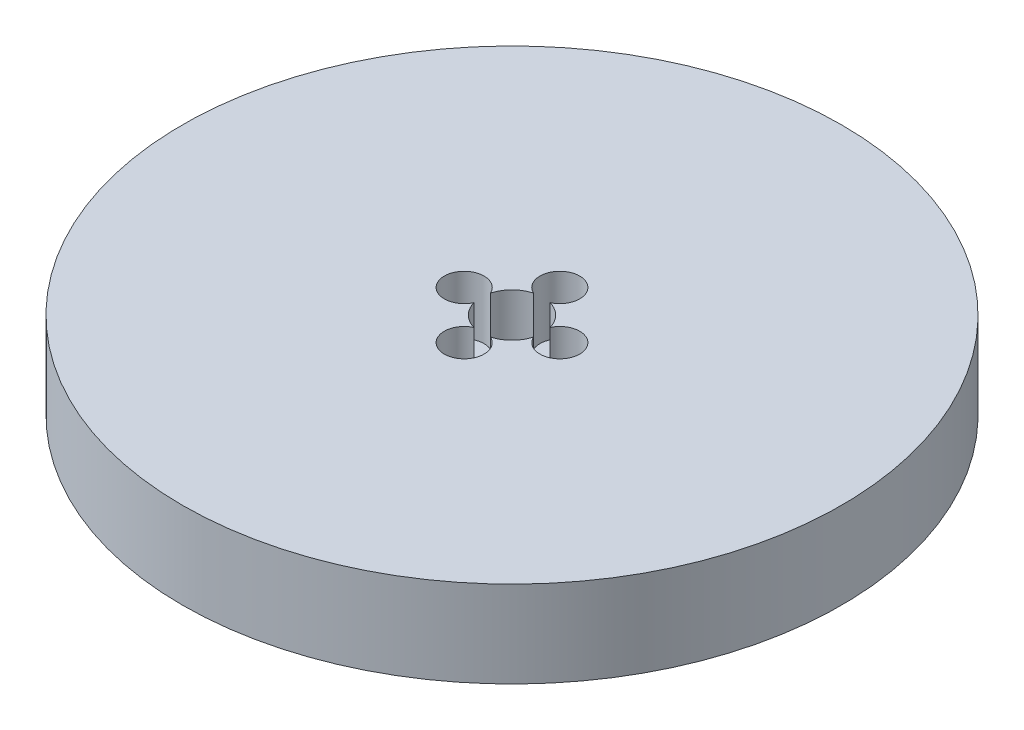
SolidWorks part; units mm, degrees
ref_plane "Front Plane" through (0, 0, 0) normal (0, 0, 1) x (1, 0, 0)
ref_plane "Top Plane" through (0, 0, 0) normal (0, 1, 0) x (1, 0, 0)
ref_plane "Right Plane" through (0, 0, 0) normal (1, 0, 0) x (0, 0, -1)
sketch "Sketch1" plane through (0, 0, 0) normal (0, 1, 0) x (1, 0, 0)
  circle A0 centre (0, 0) radius 80
  dimension "FLANGE_OD" = 160
extrude "Boss-Extrude1" add sketch "Sketch1" along normal blind 21
sketch "Sketch2" plane through (0, 0, 0) normal (0, 1, 0) x (1, 0, 0)
  circle A0 centre (0, 0) radius 7.5
  dimension "BORE_D" = 15
extrude "Cut-Extrude1" cut sketch "Sketch2" along normal through all
sketch "Sketch3" plane through (0, 21, 0) normal (0, 1, 0) x (1, 0, 0)
  circle A0 centre (0, 0) radius 11.6083 construction
  circle A1 centre (-11.6083, 0) radius 4.8197
  dimension "BOLT_D" = 9.6394
  dimension "BOLT_PCD" = 23.2166
extrude "Cut-Extrude2" cut sketch "Sketch3" against normal blind 14.2178
pattern_circular "CirPattern1" count 4 over 360 about axis through (0, 0, 0) along (0, 1, 0) of "Cut-Extrude2"
